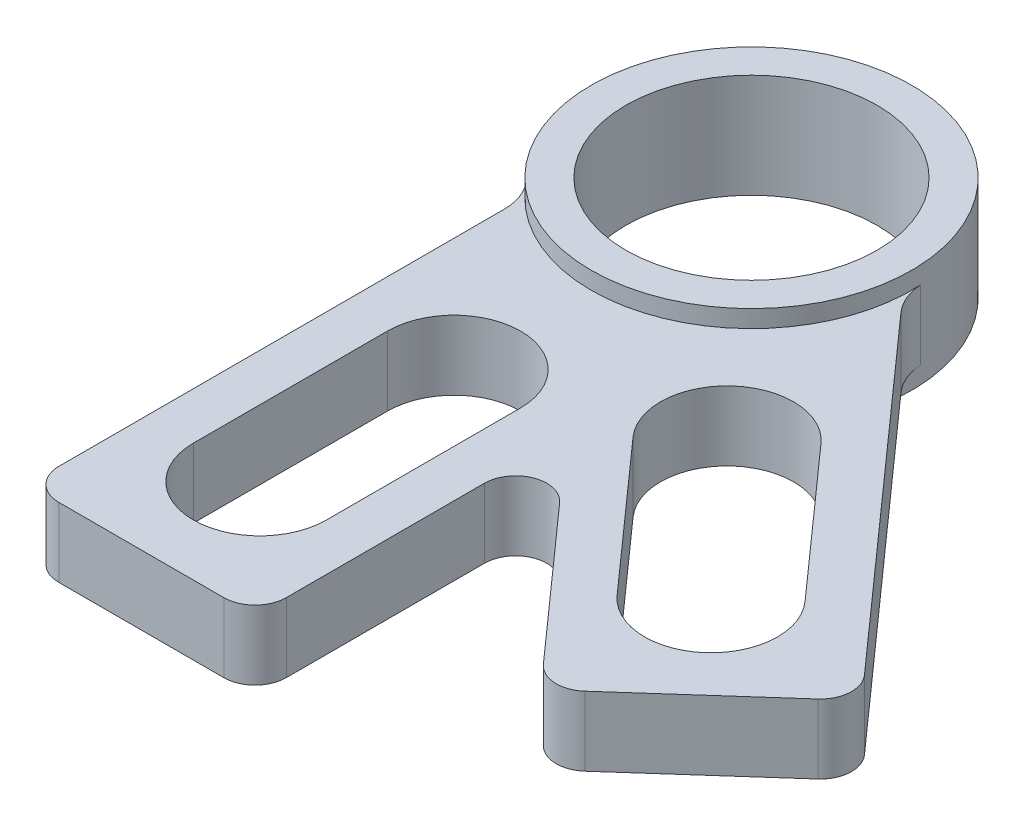
SolidWorks part; units mm, degrees
material "AISI 4130 Steel, annealed at 865C"
ref_plane "Front Plane" through (0, 0, 0) normal (0, 0, 1) x (1, 0, 0)
ref_plane "Top Plane" through (0, 0, 0) normal (0, 1, 0) x (1, 0, 0)
ref_plane "Right Plane" through (0, 0, 0) normal (1, 0, 0) x (0, 0, -1)
sketch "Sketch1" plane through (0, 0, 0) normal (0, 1, 0) x (1, 0, 0)
  line L0 (0, 0) -> (0, -55.88) construction
  line L1 (0, 0) -> (37.1508, -41.7419) construction
  line L2 (0, -45.0215) -> (0, -27.2415) construction
  line L3 (-6.096, -45.0215) -> (-6.096, -27.2415)
  line L4 (6.096, -45.0215) -> (6.096, -27.2415)
  line L5 (29.9318, -33.6307) -> (18.111, -20.3492) construction
  line L6 (25.3781, -37.6835) -> (13.5574, -24.402)
  line L7 (34.4854, -29.5779) -> (22.6647, -16.2964)
  line L8 (0, -55.88) -> (0, -51.1175) construction
  line L9 (37.1508, -41.7419) -> (33.9846, -38.1844) construction
  line L10 (-10.414, -55.88) -> (10.414, -55.88)
  line L11 (29.3717, -48.6655) -> (44.93, -34.8184)
  line L12 (-10.414, -55.88) -> (-10.414, -10.3482)
  line L13 (10.414, -55.88) -> (10.414, -27.3651)
  line L14 (44.93, -34.8184) -> (14.659, -0.8065)
  line L15 (29.3717, -48.6655) -> (10.414, -27.3651)
  line L16 (196.1691, -220.4118) -> (16.6401, -18.6965) construction
  line L22 (0, 0) -> (10.414, -27.3651) construction
  circle A0 centre (0, 0) radius 11.5062
  circle A1 centre (0, 0) radius 14.6812
  arc A2 (-6.096, -45.0215) -> (6.096, -45.0215) centre (0, -45.0215) ccw
  arc A3 (6.096, -27.2415) -> (-6.096, -27.2415) centre (0, -27.2415) ccw
  arc A4 (25.3781, -37.6835) -> (34.4854, -29.5779) centre (29.9318, -33.6307) ccw
  arc A5 (22.6647, -16.2964) -> (13.5574, -24.402) centre (18.111, -20.3492) ccw
  point P8 (0, -36.1315)
  point P13 (24.0214, -26.99)
  point P25 (0, -55.88)
  point P27 (37.1508, -41.7419)
  dimension "D2" = 29.3624
  dimension "D3" = 4.7625
  dimension "D4" = 4.318
  dimension "D5" = 17.78
  dimension "D6" = 55.88
  dimension "D7" = 20.828
extrude "Bearing_Insert_Extrude" add sketch "Sketch1" along normal mid plane 9.525 contours A1 A0 region at (-5.4385, 0, -13.1886)
extrude "Apex_Slot_Insert_Extrude" add sketch "Sketch1<4>" along normal mid plane 6.35 contours A1 L12 L10 L13 L15 L11 L14 A5 L7 A4 L6 A3 L4 A2 L3 region at (-9.6332, 0, 33.1141)
sketch "Sketch1<4>" plane through (0, 0, 0) normal (0, 1, 0) x (1, 0, 0) same geometry as "Sketch1"
fillet "Fillet1" radius 5.08 2 edges at (14.659, 0, 0.8065) (-10.414, 0, 10.3482)
fillet "Fillet2" radius 2.8575 5 edges at (44.93, 0, 34.8184) (29.3717, 0, 48.6655) (10.414, 0, 27.3651) (10.414, 0, 55.88) (-10.414, 0, 55.88)
equation "\"Apex_thickness\"= .25"
equation "\"Bearing_diameter\"= 0.906in"
equation "\"A-arm_angle\"= 39.1893"
equation "\"D1@Sketch1\"=\"Bearing_diameter\""
equation "\"D1@Apex_Slot_Insert_Extrude\"=\"Apex_thickness\""
